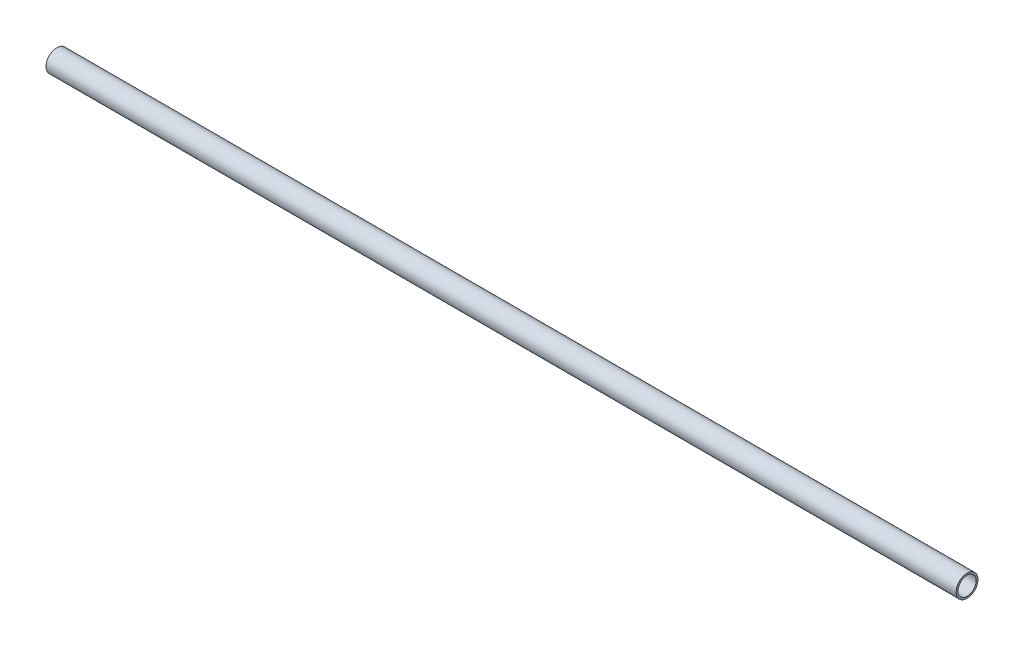
SolidWorks part; units mm, degrees
material "Thornel Mat VMA"
ref_plane "Ön Düzlem" through (0, 0, 0) normal (0, 0, 1) x (1, 0, 0)
ref_plane "Üst Düzlem" through (0, 0, 0) normal (0, 1, 0) x (1, 0, 0)
ref_plane "Sağ Düzlem" through (0, 0, 0) normal (1, 0, 0) x (0, 0, -1)
sketch "Çizim1" plane through (0, 0, 0) normal (1, 0, 0) x (0, 0, -1)
  circle A0 centre (0, 0) radius 6
  circle A1 centre (0, 0) radius 5
  dimension "D1" = 12
  dimension "D2" = 10
extrude "Yükseklik-Ekstrüzyon1" add sketch "Çizim1" along normal mid plane 500
sketch "Çizim2" plane through (250, 0, 0) normal (1, 0, 0) x (0, 0, -1)
  line L0 (0, -6) -> (0, 6) construction
  circle A0 centre (0, 0) radius 6 construction
  point P7 (0, 0)
